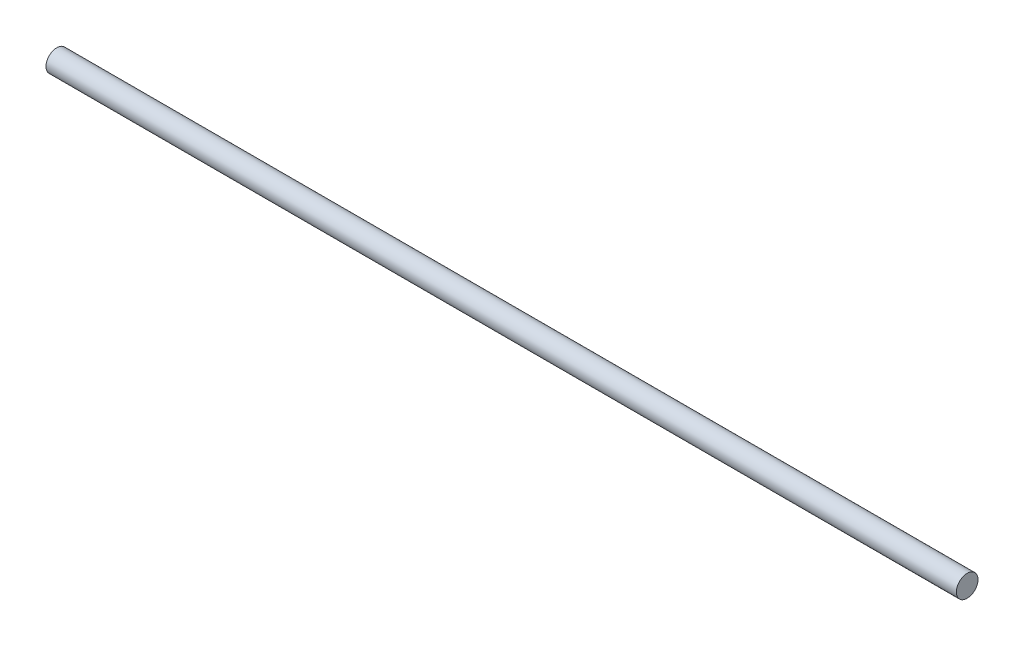
SolidWorks part; units mm, degrees
ref_plane "Front Plane" through (0, 0, 0) normal (0, 0, 1) x (1, 0, 0)
ref_plane "Top Plane" through (0, 0, 0) normal (0, 1, 0) x (1, 0, 0)
ref_plane "Right Plane" through (0, 0, 0) normal (1, 0, 0) x (0, 0, -1)
sketch "Sketch1" plane through (0, 0, 0) normal (1, 0, 0) x (0, 0, -1)
  circle A0 centre (0, 0) radius 1.25
  dimension "D1" = 2.5
extrude "Boss-Extrude1" add sketch "Sketch1" along normal blind 105
